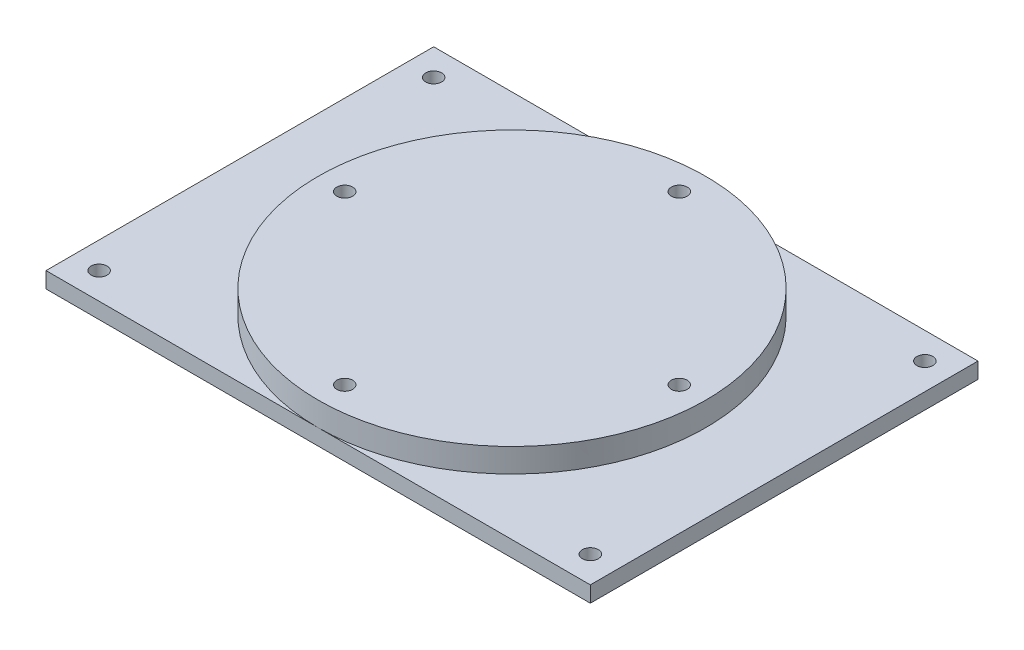
SolidWorks part; units mm, degrees
ref_plane "Front Plane" through (0, 0, 0) normal (0, 0, 1) x (1, 0, 0)
ref_plane "Top Plane" through (0, 0, 0) normal (0, 1, 0) x (1, 0, 0)
ref_plane "Right Plane" through (0, 0, 0) normal (1, 0, 0) x (0, 0, -1)
sketch "Sketch1" plane through (0, 0, 0) normal (0, 1, 0) x (1, 0, 0)
  line L0 (-51.25, 36.5) -> (51.25, 36.5)
  line L1 (-46.25, 31.5) -> (46.25, 31.5)
  line L2 (-46.25, 31.5) -> (-46.25, -31.5)
  line L3 (-46.25, -31.5) -> (46.25, -31.5)
  line L4 (46.25, 31.5) -> (46.25, -31.5)
  line L5 (-46.25, 31.5) -> (46.25, -31.5) construction
  line L6 (-46.25, -31.5) -> (46.25, 31.5) construction
  line L7 (51.25, 36.5) -> (51.25, -36.5)
  line L8 (-51.25, -36.5) -> (51.25, -36.5)
  line L9 (-51.25, 36.5) -> (-51.25, -36.5)
  line L10 (-46.25, -31.5) -> (46.25, 31.5)
  line L11 (46.25, -31.5) -> (-46.25, 31.5)
  line L12 (-36.5, 0) -> (36.5, 0)
  line L13 (0, -36.5) -> (0, 36.5)
  circle A0 centre (-46.25, 31.5) radius 1.5
  circle A1 centre (46.25, 31.5) radius 1.5
  circle A2 centre (46.25, -31.5) radius 1.5
  circle A3 centre (-46.25, -31.5) radius 1.5
  circle A4 centre (0, 0) radius 36.5
  circle A5 centre (0, 0) radius 31.5
  circle A14 centre (0, 31.5) radius 1.5
  circle A15 centre (-31.5, 0) radius 1.5
  circle A16 centre (0, -31.5) radius 1.5
  circle A17 centre (31.5, 0) radius 1.5
  circle A18 centre (-31.5, 0) radius 3.25
  circle A19 centre (0, -31.5) radius 3.25
  circle A20 centre (31.5, 0) radius 3.25
  circle A21 centre (0, 31.5) radius 3.25
  point P0 (0, 0)
  point P21 (26.0351, -17.732)
  dimension "D4" = 3
  dimension "D5" = 73
  dimension "D6" = 63
  dimension "D7" = 3
  dimension "D8" = 6.5
  dimension "D1" = 92.5
  dimension "D2" = 63
  dimension "D3" = 5
extrude "Boss-Extrude3" add sketch "Sketch1" along normal blind 3 contours A4 L0 L9 L8 L3 A3 L2 A0 L1 | A4 L11 A0 L2 A3 L10 | A4 L1 A0 L11 | A4 L1 A1 L4 A2 L3 L8 L7 L0 | A4 L10 A1 L1 | A4 L11 A2 L4 A1 L10 | A4 L3 A2 L11 | A4 L10 A3 L3 region at (-25.625, 0, -35.6081) region at (25.625, 0, -35.6081) region at (32.0308, 0, -27.9384) region at (-32.0308, 0, -27.9384) region at (40.3749, 0, 0) region at (-40.3749, 0, 0) region at (-32.0308, 0, 27.9384) region at (32.0308, 0, 27.9384)
extrude "Boss-Extrude4" add sketch "Sketch1<7>" along normal blind 7.5 contours L12 A18 A5 A15 | A5 A18 L12 A15 | L12 A18 A5 A15 | A5 A18 L12 A15 | A5 A20 L12 A17 | L12 A20 A5 A17 | A5 A20 L12 A17 | L12 A20 A5 A17 | A5 A19 L13 A16 | L13 A19 A5 A16 | L3 A19 L13 A16 | L13 A19 L3 A16 | A5 A19 L3 A16 | L3 A19 A5 A16 | L1 A21 A5 A14 | L13 A21 L1 A14 | A5 A21 L13 A14 | A5 A21 L1 A14 | L1 A21 L13 A14 | L13 A21 A5 A14 | A21 A5 L10 A4 L1 | A21 L1 A4 L11 A5 | A18 A5 L11 A4 L12 | A18 L12 A4 L10 A5 | A19 A5 L10 A4 L3 | A20 A5 L11 A4 L12 | A19 L3 A4 L11 A5 | A19 L13 A4 L3 | A19 L3 A4 L13 | A19 A5 L11 L13 | A20 L12 L11 A5 | A20 A5 L10 L12 | A21 A5 L11 L13 | A21 L13 L10 A5 | A18 L12 L11 A5 | A18 A5 L10 L12 | A19 L13 L10 A5 | A20 L12 A4 L10 A5 | A21 L13 A4 L1 | A21 L1 A4 L13 region at (7.8423, 0, -33.6093) region at (-7.8423, 0, -33.6093) region at (1.5804, 0, -33.0804) region at (-1.5804, 0, -33.0804) region at (20.3696, 0, -26.1582) region at (-20.3696, 0, -26.1582) region at (-7.8423, 0, 33.6093) region at (7.8423, 0, 33.6093) region at (2.5799, 0, -31.4454) region at (-2.5799, 0, -31.4454) region at (31.9967, 0, -10.6548) region at (-31.9967, 0, -10.6548) region at (-1.5804, 0, 33.0804) region at (1.5804, 0, 33.0804) region at (-20.3696, 0, 26.1582) region at (20.3696, 0, 26.1582) region at (1.5547, 0, -29.8803) region at (9.5727, 0, -17.6311) region at (-9.5727, 0, -17.6311) region at (-1.5547, 0, -29.8803) region at (19.4807, 0, -6.2265) region at (31.9967, 0, 10.6548) region at (-19.4807, 0, -6.2265) region at (-31.9967, 0, 10.6548) region at (-2.5799, 0, 31.4454) region at (2.5799, 0, 31.4454) region at (-9.5727, 0, 17.6311) region at (19.4807, 0, 6.2265) region at (-19.4807, 0, 6.2265) region at (9.5727, 0, 17.6311) region at (33.0404, 0, -1.6048) region at (29.8803, 0, -1.5547) region at (33.0404, 0, 1.6048) region at (-29.8803, 0, -1.5547) region at (-33.0404, 0, -1.6048) region at (-33.0404, 0, 1.6048) region at (-1.5547, 0, 29.8803) region at (1.5547, 0, 29.8803) region at (-29.8803, 0, 1.5547) region at (29.8803, 0, 1.5547)
sketch "Sketch1<7>" plane through (0, 0, 0) normal (0, 1, 0) x (1, 0, 0) same geometry as "Sketch1"
extrude "Cut-Extrude2" cut sketch "Sketch1<9>" along normal blind 2.5 contours L13 A21 L1 A14 | L1 A21 A5 A14 | A5 A21 L13 A14 | L1 A21 L13 A14 | L13 A21 A5 A14 | A5 A21 L1 A14 | A5 A18 L12 A15 | L12 A18 A5 A15 | A5 A18 L12 A15 | L12 A18 A5 A15 | L3 A19 L13 A16 | L13 A19 A5 A16 | A5 A19 L13 A16 | L13 A19 L3 A16 | L3 A19 A5 A16 | A5 A19 L3 A16 | L12 A20 A5 A17 | L12 A20 A5 A17 | A5 A20 L12 A17 | A5 A20 L12 A17 region at (1.5804, 0, -33.0804) region at (-1.5804, 0, -33.0804) region at (2.5799, 0, -31.4454) region at (-2.5799, 0, -31.4454) region at (-1.5804, 0, 33.0804) region at (1.5804, 0, 33.0804) region at (1.5547, 0, -29.8803) region at (-1.5547, 0, -29.8803) region at (-2.5799, 0, 31.4454) region at (2.5799, 0, 31.4454) region at (33.0404, 0, -1.6048) region at (29.8803, 0, -1.5547) region at (33.0404, 0, 1.6048) region at (-29.8803, 0, -1.5547) region at (-33.0404, 0, -1.6048) region at (-33.0404, 0, 1.6048) region at (-1.5547, 0, 29.8803) region at (1.5547, 0, 29.8803) region at (-29.8803, 0, 1.5547) region at (29.8803, 0, 1.5547)
sketch "Sketch1<9>" plane through (0, 0, 0) normal (0, 1, 0) x (1, 0, 0) same geometry as "Sketch1"
